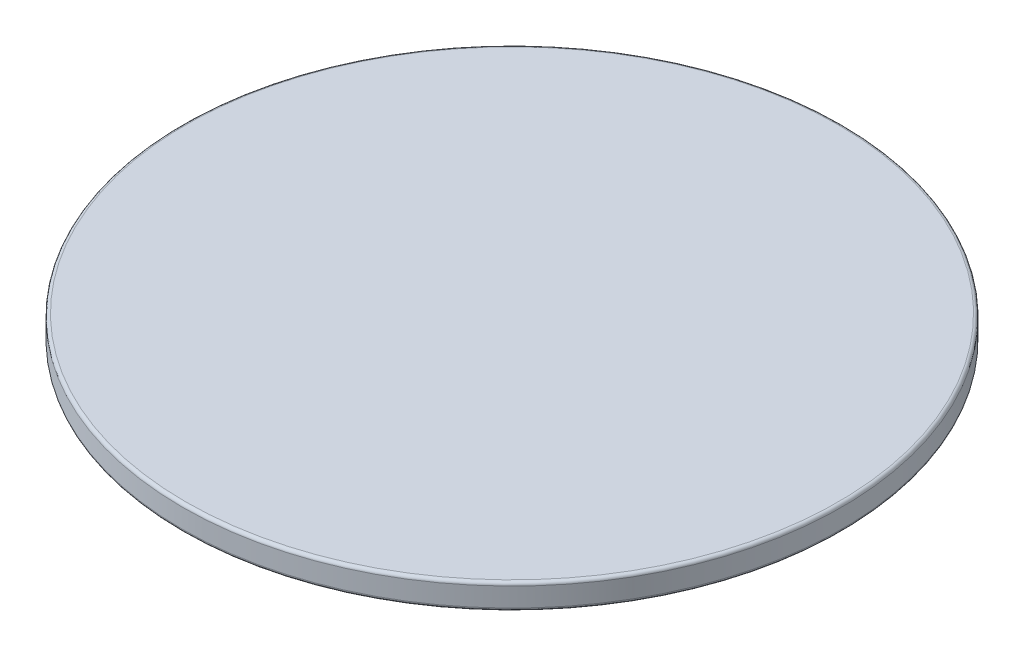
SolidWorks part; units mm, degrees
ref_plane "Front" through (0, 0, 0) normal (0, 0, 1) x (1, 0, 0)
ref_plane "Top" through (0, 0, 0) normal (0, 1, 0) x (1, 0, 0)
ref_plane "Right" through (0, 0, 0) normal (1, 0, 0) x (0, 0, -1)
sketch "Sketch2" plane through (0, 0, 0) normal (0, 1, 0) x (1, 0, 0)
  circle A0 centre (0, 0) radius 66.04
  dimension "D1" = 132.08
extrude "Boss-Extrude1" add sketch "Sketch2" along normal blind 5.08
fillet "Fillet1" radius 0.635 2 edges at (0, 0, 66.04) (0, 5.08, 66.04)
sketch "Sketch3" plane through (0, 0, 0) normal (0, -1, 0) x (1, 0, 0)
  line L0 (75.9093, 0) -> (-75.3573, 0) construction
  line L1 (0, -77.1055) -> (0, 79.4978) construction
  line L2 (13.8937, 0) -> (13.8937, 60.96) construction
  line L3 (-6.35, 76.1854) -> (6.35, 76.1854)
  line L4 (6.35, 76.1854) -> (6.35, 60.96)
  line L5 (6.35, 60.96) -> (-6.35, 60.96)
  line L6 (-6.35, 60.96) -> (-6.35, 76.1854)
  line L7 (60.96, 6.35) -> (76.1854, 6.35)
  line L8 (76.1854, 6.35) -> (76.1854, -6.35)
  line L9 (76.1854, -6.35) -> (60.96, -6.35)
  line L10 (60.96, -6.35) -> (60.96, 6.35)
  line L11 (6.35, -60.96) -> (6.35, -76.1854)
  line L12 (6.35, -76.1854) -> (-6.35, -76.1854)
  line L13 (-6.35, -76.1854) -> (-6.35, -60.96)
  line L14 (-6.35, -60.96) -> (6.35, -60.96)
  line L15 (-60.96, -6.35) -> (-76.1854, -6.35)
  line L16 (-76.1854, -6.35) -> (-76.1854, 6.35)
  line L17 (-76.1854, 6.35) -> (-60.96, 6.35)
  line L18 (-60.96, 6.35) -> (-60.96, -6.35)
  point P10 (0, 76.1854)
  point P27 (0, 0)
  dimension "D1" = 60.96
  dimension "D2" = 6.35
  dimension "D3" = 4
